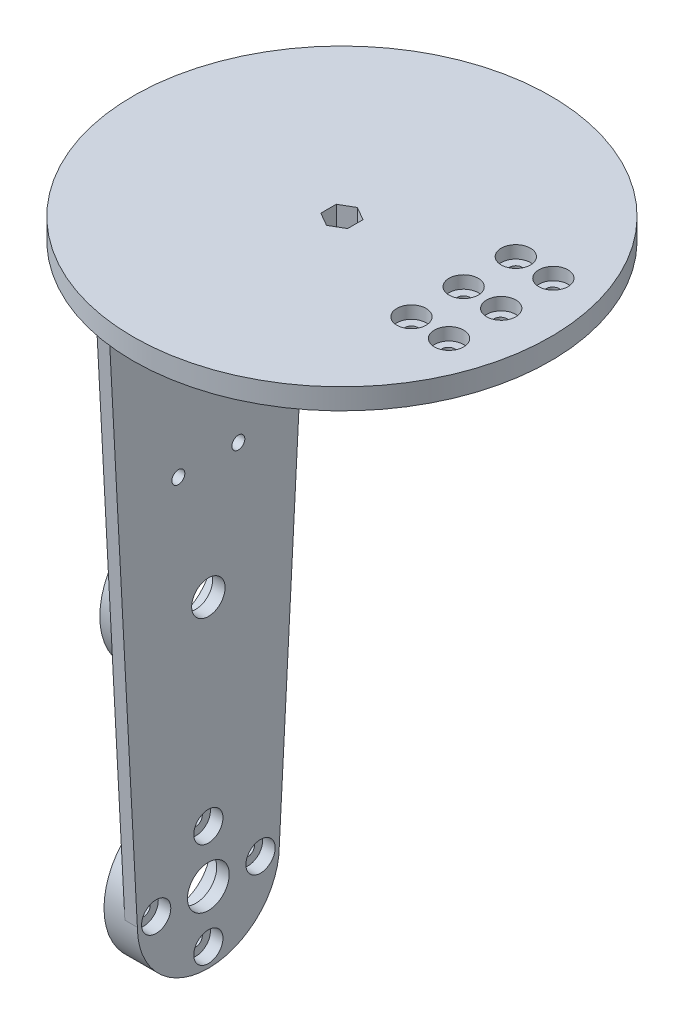
SolidWorks part; units mm, degrees
ref_plane "Front Plane" through (0, 0, 0) normal (0, 0, 1) x (1, 0, 0)
ref_plane "Top Plane" through (0, 0, 0) normal (0, 1, 0) x (1, 0, 0)
ref_plane "Right Plane" through (0, 0, 0) normal (1, 0, 0) x (0, 0, -1)
sketch "Sketch2" plane through (0, 0, 0) normal (0, 1, 0) x (1, 0, 0)
  circle A0 centre (0, 0) radius 9
extrude "Boss-Extrude1" add sketch "Sketch2" along normal blind 20
sketch "Sketch3" plane through (0, 20, 0) normal (0, 1, 0) x (1, 0, 0)
  line L0 (-3.2043, -1.85) -> (3.2043, 1.85) construction
  line L1 (0, -3.7) -> (0, 3.7) construction
  line L2 (3.2043, -1.85) -> (-3.2043, 1.85) construction
  line L15 (0, 3.7) -> (-3.2043, 1.85)
  line L16 (-3.2043, 1.85) -> (-3.2043, -1.85)
  line L17 (-3.2043, -1.85) -> (0, -3.7)
  line L18 (0, -3.7) -> (3.2043, -1.85)
  line L19 (3.2043, -1.85) -> (3.2043, 1.85)
  line L20 (3.2043, 1.85) -> (0, 3.7)
  circle A0 centre (0, 0) radius 3.7 construction
  point P4 (0, 0)
  point P5 (0, 0)
  point P6 (0, 0)
  point P9 (0, 0)
  point P10 (0, 0)
  point P11 (0, 0)
  point P14 (0, 0)
  point P15 (0, 0)
  point P17 (0, 0)
  point P20 (0, 0)
extrude "Cut-Extrude1" cut sketch "Sketch3" against normal blind 20
sketch "Sketch4" plane through (0, 20, 0) normal (0, 1, 0) x (1, 0, 0)
  circle A0 centre (0, 0) radius 50
  circle A1 centre (0, 0) radius 4.5
extrude "Boss-Extrude3" add sketch "Sketch4" against normal blind 5
ref_plane "Plane3" through (0, 0, 0) normal (0.5, 0, 0.866) x (0.866, 0, -0.5)
sketch "Sketch11" plane through (0, 0, 0) normal (0.5, 0, 0.866) x (0.866, 0, -0.5)
  line L2 (0, 0) -> (0, 5) construction
  circle A0 centre (0, 5) radius 1.55
extrude "Cut-Extrude2" cut sketch "Sketch11" against normal blind 9 and the other way blind 9
ref_plane "Plane4" through (0, 0, 0) normal (1, 0, 0) x (0, 0, -1)
sketch "Sketch15" plane through (0, 0, 0) normal (1, 0, 0) x (0, 0, -1)
  line L0 (0, 0) -> (0, 9) construction
  circle A0 centre (0, 9) radius 1.55
extrude "Cut-Extrude9" cut sketch "Sketch15" against normal blind 9 and the other way blind 9
sketch "Sketch16" plane through (0, 15, 0) normal (0, -1, 0) x (1, 0, 0)
  line L0 (0, 0) -> (32, 0) construction
  line L6 (0, 0) -> (-32, 0) construction
  line L7 (-32, -25) -> (-32, 25) construction
  line L8 (32, 25) -> (32, -25) construction
  line L9 (32, 25) -> (35, 25) construction
  line L10 (32, -25) -> (35, -25) construction
  line L11 (35, 25) -> (35, -25) construction
  line L12 (32, 25) -> (35, -25) construction
  line L13 (32, -25) -> (35, 25) construction
  line L14 (32, 25) -> (26.3083, 25) construction
  line L15 (35, 25) -> (41, 25) construction
  line L16 (29.1541, 25) -> (29.1541, 12.5) construction
  line L17 (29.1541, 12.5) -> (29.1541, 0) construction
  line L18 (29.1541, 0) -> (29.1541, -12.5) construction
  line L19 (38, 25) -> (38, 12.5) construction
  line L20 (38, 12.5) -> (38, 0) construction
  line L21 (38, 0) -> (38, -12.5) construction
  circle A0 centre (29.1541, 12.5) radius 1.55
  circle A1 centre (29.1541, 0) radius 1.55
  circle A2 centre (29.1541, -12.5) radius 1.55
  circle A3 centre (38, -12.5) radius 1.55
  circle A4 centre (38, 0) radius 1.55
  circle A5 centre (38, 12.5) radius 1.55
  point P8 (32, 0)
  point P10 (-32, 0)
  point P14 (33.5, 0)
ref_plane "Plane7" through (-32, 0, 0) normal (-1, 0, 0) x (0, 0, 1)
sketch "Sketch28" plane through (-32, 0, 0) normal (-1, 0, 0) x (0, 0, 1)
  line L0 (25, 15) -> (-25, 15)
  line L1 (0, -135) -> (0, -75) construction
  line L2 (-50, 15) -> (50, 15) construction
  line L3 (0, 15) -> (0, -135) construction
  line L6 (25, 15) -> (17, -135)
  line L7 (-17, -135) -> (-25, 15)
  circle A0 centre (0, -135) radius 5
  circle A3 centre (0, -75) radius 4
  arc A6 (17, -135) -> (-17, -135) centre (0, -135) cw
  circle A8 centre (7.1867, -46.5) radius 1.55
  circle A9 centre (-7.1867, -46.5) radius 1.55
  point P4 (0, 15)
extrude "Boss-Extrude10" add sketch "Sketch28" along normal blind 3
sketch "Sketch25" plane through (-35, 0, 0) normal (-1, 0, 0) x (0, 0, 1)
  circle A6 centre (0, -135) radius 8.5
  circle A7 centre (0, -135) radius 17
extrude "Boss-Extrude8" add sketch "Sketch25" along normal blind 5
sketch "Sketch26" plane through (-40, 0, 0) normal (-1, 0, 0) x (0, 0, 1)
  circle A12 centre (0, -135) radius 12.5 construction
  circle A16 centre (-12.5, -135) radius 1.55
  circle A17 centre (0, -122.5) radius 1.55
  circle A18 centre (12.5, -135) radius 1.55
  circle A19 centre (0, -147.5) radius 1.55
  point P14 (0, -135)
extrude "Cut-Extrude14" cut sketch "Sketch26" against normal blind 8
sketch "Sketch27" plane through (-32, 0, 0) normal (1, 0, 0) x (0, 0, -1)
  circle A4 centre (0, -135) radius 12.5 construction
  circle A5 centre (-12.5, -135) radius 3.5
  circle A6 centre (0, -122.5) radius 3.5
  circle A7 centre (12.5, -135) radius 3.5
  circle A8 centre (0, -147.5) radius 3.5
  point P15 (0, -135)
  dimension "D1" = 4
extrude "Cut-Extrude15" cut sketch "Sketch27" against normal blind 3
extrude "Cut-Extrude17" cut sketch "Sketch16" against normal blind 5
sketch "Sketch29" plane through (0, 20, 0) normal (0, 1, 0) x (1, 0, 0)
  circle A0 centre (29.1541, 12.5) radius 3.5
  circle A1 centre (38.1541, 12.5) radius 3.5
  circle A2 centre (38.1541, 0) radius 3.5
  circle A3 centre (38.1541, -12.5) radius 3.5
  circle A4 centre (29.1541, 0) radius 3.5
  circle A5 centre (29.1541, -12.5) radius 3.5
  dimension "D1" = 2
  dimension "D2" = 3
extrude "Cut-Extrude18" cut sketch "Sketch29" against normal blind 3
sketch "Sketch30" plane through (-35, 0, 0) normal (-1, 0, 0) x (0, 0, 1)
  circle A0 centre (0, -75) radius 10
  circle A1 centre (0, -75) radius 17
extrude "Boss-Extrude11" add sketch "Sketch30" along normal blind 6
sketch "Sketch31" plane through (0, 0, 0) normal (0.5, 0, 0.866) x (0.866, 0, -0.5)
  circle A1 centre (0, 5) radius 3.5
extrude "Cut-Extrude23" cut sketch "Sketch31" against normal blind 2.5 from offset 9
extrude "Cut-Extrude24" cut sketch "Sketch31<3>" along normal blind 2.5 from offset 9 offset against normal yes
sketch "Sketch31<3>" plane through (0, 0, 0) normal (0.5, 0, 0.866) x (0.866, 0, -0.5) same geometry as "Sketch31"
sketch "Sketch33" plane through (0, 0, 0) normal (1, 0, 0) x (0, 0, -1)
  circle A0 centre (0, 9) radius 3.5
extrude "Cut-Extrude25" cut sketch "Sketch33" against normal blind 2.5 from offset 9
extrude "Cut-Extrude26" cut sketch "Sketch33<2>" along normal blind 2.5 from offset 9 offset against normal yes
sketch "Sketch33<2>" plane through (0, 0, 0) normal (1, 0, 0) x (0, 0, -1) same geometry as "Sketch33"
